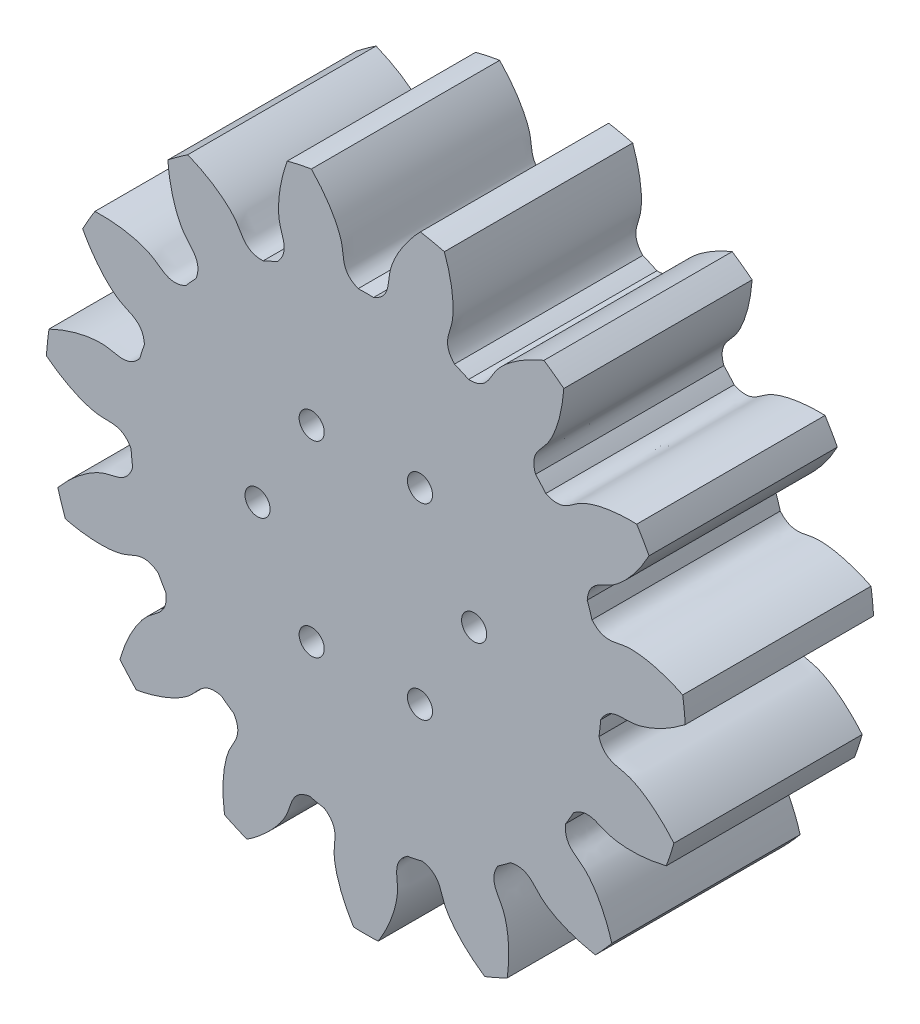
SolidWorks part; units mm, degrees
ref_plane "前视基准面" through (0, 0, 0) normal (0, 0, 1) x (1, 0, 0)
ref_plane "上视基准面" through (0, 0, 0) normal (0, 1, 0) x (1, 0, 0)
ref_plane "右视基准面" through (0, 0, 0) normal (1, 0, 0) x (0, 0, -1)
sketch "草图1" plane through (0, 0, 0) normal (0, 0, 1) x (1, 0, 0)
  circle A0 centre (0, 0) radius 51
extrude "凸台-拉伸1" add sketch "草图1" along normal blind 30
ref_axis "基准轴1" through (0, 0, -1.5) along (0, 0, 1)
sketch "草图2" plane through (0, 0, 0) normal (0, 0, 1) x (1, 0, 0)
  line L0 (0, 0) -> (0, 51) construction
  circle A0 centre (0, 0) radius 51 construction
  arc A1 (1.2257, 37.48) -> (-1.2257, 37.48) centre (0, 0) ccw
  arc A2 (19.481, 57.8156) -> (-19.481, 57.8156) centre (0, 0) ccw
  spline S0 degree 3 poles (1.2257, 37.48) (3.9433, 38.6065) (3.4327, 40.718) (3.9076, 42.651) (3.9446, 42.7899) (3.9891, 42.9444) (4.0417, 43.114) (4.1029, 43.2986) (4.1735, 43.4979) (4.2541, 43.7116) (4.3451, 43.9394) (4.4473, 44.1808) (4.5612, 44.4356) (4.6873, 44.7034) (4.8263, 44.9838) (4.9787, 45.2763) (5.1451, 45.5806) (5.3258, 45.8962) (5.5216, 46.2226) (5.7328, 46.5593) (5.96, 46.9059) (6.2036, 47.2619) (6.4642, 47.6266) (6.742, 47.9997) (7.0377, 48.3805) (7.3515, 48.7684) (7.6839, 49.163) (8.0353, 49.5635) (8.4061, 49.9694) (8.7965, 50.3801) (9.207, 50.7949) (9.6379, 51.2132) (10.0893, 51.6344) (10.5617, 52.0577) (11.0553, 52.4825) (11.5704, 52.9082) (12.1071, 53.3339) (12.6656, 53.7591) (13.2462, 54.1831) (13.849, 54.605) (14.4742, 55.0242) (15.1219, 55.44) (15.7922, 55.8516) (16.4852, 56.2582) (17.2009, 56.6592) (18.1955, 57.1906) (18.9609, 57.5702) (19.481, 57.8156) knots 0 0 0 0 0.202473 0.206979 0.212085 0.217793 0.224101 0.23101 0.23852 0.24663 0.255341 0.264653 0.274566 0.285079 0.296194 0.307909 0.320225 0.333141 0.346659 0.360777 0.375496 0.390816 0.406736 0.423257 0.440379 0.458102 0.476426 0.49535 0.514875 0.535001 0.555728 0.577055 0.598984 0.621513 0.644642 0.668373 0.692704 0.717636 0.743169 0.769303 0.796037 0.823373 0.851309 0.879845 0.908983 0.938721 1 1 1 1
  spline S1 degree 3 poles (-1.2257, 37.48) (-3.9433, 38.6065) (-3.4327, 40.718) (-3.9076, 42.651) (-3.9446, 42.7899) (-3.9891, 42.9444) (-4.0417, 43.114) (-4.1029, 43.2986) (-4.1735, 43.4979) (-4.2541, 43.7116) (-4.3451, 43.9394) (-4.4473, 44.1808) (-4.5612, 44.4356) (-4.6873, 44.7034) (-4.8263, 44.9838) (-4.9787, 45.2763) (-5.1451, 45.5806) (-5.3258, 45.8962) (-5.5216, 46.2226) (-5.7328, 46.5593) (-5.96, 46.9059) (-6.2036, 47.2619) (-6.4642, 47.6266) (-6.742, 47.9997) (-7.0377, 48.3805) (-7.3515, 48.7684) (-7.6839, 49.163) (-8.0353, 49.5635) (-8.4061, 49.9694) (-8.7965, 50.3801) (-9.207, 50.7949) (-9.6379, 51.2132) (-10.0893, 51.6344) (-10.5617, 52.0577) (-11.0553, 52.4825) (-11.5704, 52.9082) (-12.1071, 53.3339) (-12.6656, 53.7591) (-13.2462, 54.1831) (-13.849, 54.605) (-14.4742, 55.0242) (-15.1219, 55.44) (-15.7922, 55.8516) (-16.4852, 56.2582) (-17.2009, 56.6592) (-18.1955, 57.1906) (-18.9609, 57.5702) (-19.481, 57.8156) knots 0 0 0 0 0.202473 0.206979 0.212085 0.217793 0.224101 0.23101 0.23852 0.24663 0.255341 0.264653 0.274566 0.285079 0.296194 0.307909 0.320225 0.333141 0.346659 0.360777 0.375496 0.390816 0.406736 0.423257 0.440379 0.458102 0.476426 0.49535 0.514875 0.535001 0.555728 0.577055 0.598984 0.621513 0.644642 0.668373 0.692704 0.717636 0.743169 0.769303 0.796037 0.823373 0.851309 0.879845 0.908983 0.938721 1 1 1 1
extrude "切除-拉伸1" cut sketch "草图2" along normal through all
pattern_circular "阵列(圆周)1" count 15 every 24 about axis through (0, 0, -1.5) along (0, 0, 1) of "切除-拉伸1"
sketch "草图3" plane through (0, 0, 0) normal (0, 0, 1) x (1, 0, 0)
  circle A0 centre (0, 0) radius 45 construction
  dimension "Dn" = 90
sketch "草图4" plane through (0, 0, 0) normal (0, 0, -1) x (-1, 0, 0)
  circle A0 centre (0, 0) radius 17.25
  circle A1 centre (-17.25, 0) radius 2
  circle A2 centre (-8.625, 14.9389) radius 2
  circle A3 centre (8.625, 14.9389) radius 2
  circle A4 centre (17.25, 0) radius 2
  circle A5 centre (8.625, -14.9389) radius 2
  circle A6 centre (-8.625, -14.9389) radius 2
  point P17 (0, 0)
  dimension "D1" = 34.5
  dimension "D2" = 6
extrude "切除-拉伸3" cut sketch "草图4" against normal blind 70 contours A2 | A3 | A1 | A4 | A5 | A6
